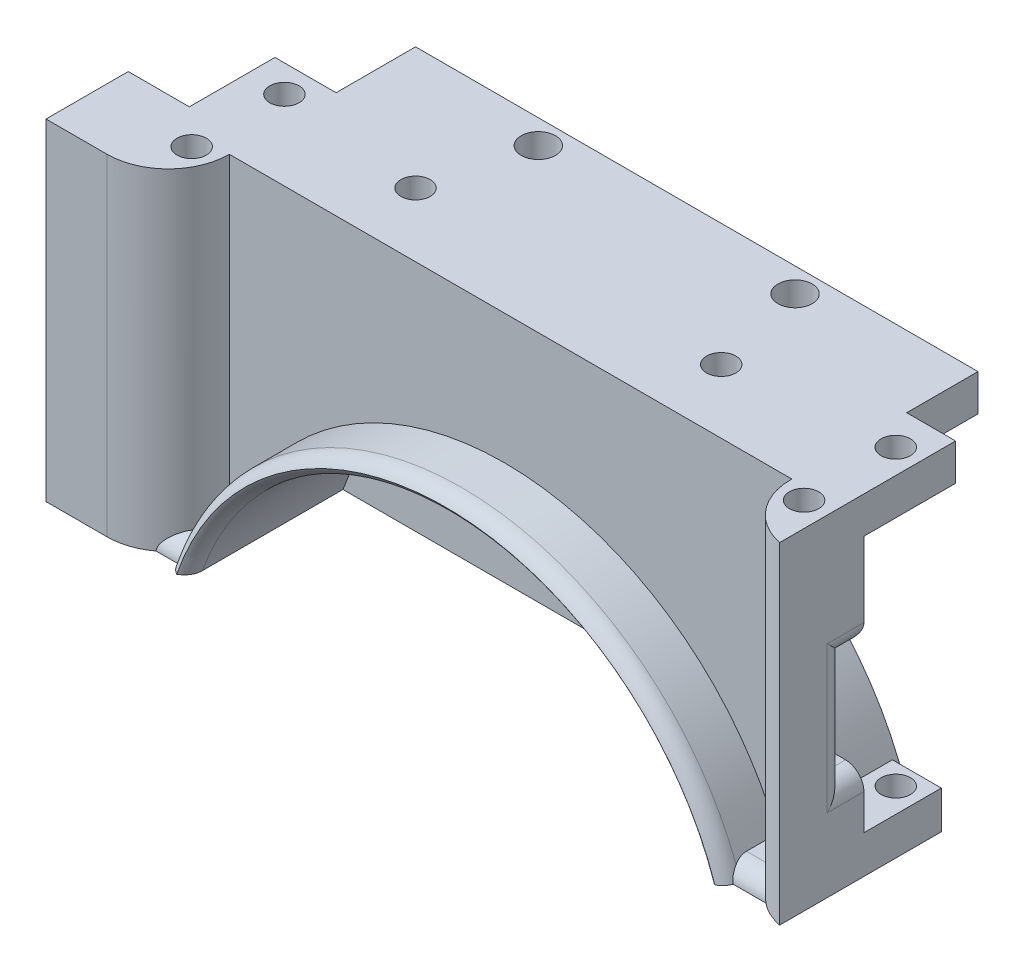
SolidWorks part; units mm, degrees
ref_plane "Front Plane" through (0, 0, 0) normal (0, 0, 1) x (1, 0, 0)
ref_plane "Top Plane" through (0, 0, 0) normal (0, 1, 0) x (1, 0, 0)
ref_plane "Right Plane" through (0, 0, 0) normal (1, 0, 0) x (0, 0, -1)
sketch "Sketch1" plane through (0, 0, 0) normal (0, 1, 0) x (1, 0, 0)
  line L0 (10, 3.275) -> (110, 3.275)
  line L1 (-10, -6.725) -> (10, -6.725)
  line L2 (-10, -6.725) -> (-10, 6.725)
  line L3 (-10, 6.725) -> (0, 6.725)
  line L4 (10, -6.725) -> (10, 3.275)
  line L5 (10, 6.725) -> (102, 6.725)
  line L6 (0, 6.725) -> (0, 20.725)
  line L7 (110, 3.275) -> (110, 6.725)
  line L8 (0, 20.725) -> (10, 20.725)
  line L9 (10, 20.725) -> (10, 6.725)
  line L10 (110, 6.725) -> (110, 19.725)
  line L11 (110, 19.725) -> (102, 19.725)
  line L12 (102, 19.725) -> (102, 6.725)
  point P0 (0, 0)
  dimension "D1" = 20
  dimension "D2" = 13.45
  dimension "D3" = 10
  dimension "D4" = 100
  dimension "D5" = 13
  dimension "D6" = 8
  dimension "D7" = 14
extrude "Boss-Extrude2" add sketch "Sketch1" along normal blind 54.2
fillet "Fillet2" radius 10 1 edges at (10, 27.1, 6.725)
sketch "Sketch2" plane through (0, 0, -3.275) normal (0, 0, 1) x (1, 0, 0)
  line L0 (10, 54.2) -> (110, 54.2) construction
  line L1 (110, 0) -> (102, 0)
  line L2 (110, 0) -> (110, 54.2)
  line L3 (110, 54.2) -> (102, 54.2)
  line L4 (102, 0) -> (102, 54.2)
  dimension "D1" = 8
extrude "Boss-Extrude3" add sketch "Sketch2" along normal blind 10
fillet "Fillet3" radius 10 1 edges at (102, 27.1, 6.725)
sketch "Sketch3" plane through (0, 0, -3.275) normal (0, 0, 1) x (1, 0, 0)
  line L1 (10, 0) -> (102, 0) construction
  line L2 (7, -15) -> (103, -15)
  line L3 (10, 54.2) -> (10, 0) construction
  arc A0 (103, -15) -> (7, -15) centre (55, -15) ccw
  dimension "D1" = 15
  dimension "D2" = 45
  dimension "D3" = 48
extrude "Boss-Extrude4" add sketch "Sketch3" along normal blind 10 and the other way blind 20
sketch "Sketch4" plane through (0, 0, 6.725) normal (0, 0, 1) x (1, 0, 0)
  line L0 (7, -15) -> (103, -15) construction
  circle A0 centre (55, -15) radius 45
  dimension "D1" = 90
extrude "Cut-Extrude1" cut sketch "Sketch4" against normal through all
sketch "Sketch5" plane through (0, 0, 6.725) normal (0, 0, 1) x (1, 0, 0)
  line L0 (9.4039, 0) -> (100.5961, 0)
  line L1 (7, -15) -> (10, -15) construction
  line L2 (10, -15) -> (105.9097, -15)
  line L3 (105.9097, -15) -> (100.5961, 0)
  arc A0 (100, -15) -> (10, -15) centre (55, -15) ccw construction
  spline S0 degree 2 poles (9.4039, 0) (-0.8331, -16.4811) (10, -15) knots 0 0 0 1 1 1
  arc M5 (10, -15) -> (100, -15) centre (55, -15) cw
extrude "Cut-Extrude2" cut sketch "Sketch5" against normal through all contours L2 L0 M5
fillet "Fillet4" radius 3 2 edges at (55, 33, 6.725) (55, 30, 6.725)
sketch "Sketch6" plane through (0, 0, -3.275) normal (0, 0, 1) x (1, 0, 0)
  line L1 (102, 0) -> (97.9701, 0)
  line L2 (102, 0) -> (102, 2.7714)
  line L3 (102, 2.7714) -> (97.9701, 2.7714)
  line L4 (97.9701, 0) -> (97.9701, 2.7714)
  arc A0 (99.0142, 0) -> (10.9858, 0) centre (55, -15) ccw construction
  dimension "D1" = 2.7714
extrude "Boss-Extrude5" add sketch "Sketch6" along normal blind 8
sketch "Sketch7" plane through (102, 0, 0) normal (1, 0, 0) x (0, 0, -1)
  line L1 (3.073, 0) -> (-4.725, 0)
  line L2 (3.073, 0) -> (3.073, 2.7714)
  line L3 (3.073, 2.7714) -> (-4.725, 2.7714)
  line L4 (-4.725, 0) -> (-4.725, 2.7714)
extrude "Boss-Extrude6" add sketch "Sketch7" along normal up to surface (3.7397 mm away)
fillet "Fillet5" radius 3 1 edges at (102.572, 2.7714, 4.725)
sketch "Sketch8" plane through (0, 0, -3.275) normal (0, 0, 1) x (1, 0, 0)
  line L1 (10.5642, 0) -> (7.2004, 0)
  line L2 (10.5642, 0) -> (10.5642, 2.77)
  line L3 (10.5642, 2.77) -> (7.2004, 2.77)
  line L4 (7.2004, 0) -> (7.2004, 2.77)
  line L5 (9.4039, 0) -> (10.9858, 0) construction
extrude "Boss-Extrude7" add sketch "Sketch8" along normal blind 8
sketch "Sketch9" plane through (7.2004, 0, 0) normal (-1, 0, 0) x (0, 0, 1)
  line L1 (3.6643, 0) -> (4.725, 0)
  line L2 (3.6643, 0) -> (3.6643, 2.77)
  line L3 (3.6643, 2.77) -> (4.725, 2.77)
  line L4 (4.725, 0) -> (4.725, 2.77)
extrude "Boss-Extrude8" add sketch "Sketch9" along normal up to surface up to face at (6.2429, 18.99, 2.8841)
fillet "Fillet12" radius 3 1 edges at (8.2821, 2.77, 4.725)
sketch "Sketch10" plane through (0, 54.2, 0) normal (0, 1, 0) x (1, 0, 0)
  line L0 (110, -6.725) -> (110, 19.725) construction
  line L1 (102, 19.725) -> (110, 19.725)
  line L2 (102, 19.725) -> (102, 13.0613)
  line L3 (102, 13.0613) -> (110, 13.0613)
  line L4 (110, 19.725) -> (110, 13.0613)
extrude "Cut-Extrude3" cut sketch "Sketch10" against normal blind 48
sketch "Sketch15" plane through (0, 0, -23.275) normal (0, 0, -1) x (-1, 0, 0)
  line L0 (-97.4264, 0) -> (-12.5736, 0)
  arc A0 (-12.5736, 0) -> (-97.4264, 0) centre (-55, -14.6489) ccw
extrude "Boss-Extrude10" add sketch "Sketch15" against normal blind 4 contours A0 L0
sketch "Sketch16" plane through (0, 0, -6.725) normal (0, 0, -1) x (-1, 0, 0)
  line L0 (-10, 54.2) -> (-10, 1.7033) construction
  line L1 (-102, 54.2) -> (-10, 54.2)
  line L2 (-102, 54.2) -> (-102, 48.2)
  line L3 (-102, 48.2) -> (-10, 48.2)
  line L4 (-10, 54.2) -> (-10, 48.2)
  dimension "D1" = 6
extrude "Boss-Extrude11" add sketch "Sketch16" along normal blind 27
sketch "Sketch17" plane through (0, 54.2, 0) normal (0, 1, 0) x (1, 0, 0)
  circle A0 centre (106, 16.275) radius 2.4
  circle A1 centre (106, 1.275) radius 2.4
  circle A2 centre (76.027, 29.775) radius 2.8
  circle A3 centre (34.027, 29.775) radius 2.8
  circle A4 centre (6, 16.275) radius 2.4
  circle A5 centre (5.83, 1.275) radius 2.4
  dimension "D1" = 4.8
  dimension "D2" = 4.8
  dimension "D3" = 4.8
  dimension "D4" = 4.8
  dimension "D5" = 5.6
  dimension "D6" = 5.6
sketch "Sketch18" plane through (0, 0, -13.0613) normal (0, 0, -1) x (-1, 0, 0)
  line L1 (-110, 54.2) -> (-102, 54.2)
  line L2 (-110, 54.2) -> (-110, 48.2)
  line L3 (-110, 48.2) -> (-102, 48.2)
  line L4 (-102, 54.2) -> (-102, 48.2)
extrude "Boss-Extrude12" add sketch "Sketch18" along normal blind 9
sketch "Sketch20" plane through (0, 0, -6.725) normal (0, 0, -1) x (-1, 0, 0)
  line L0 (-102, 43.3091) -> (-10, 43.3091) construction
  line L1 (-102, 6.2) -> (-102, 48.2) construction
  line L2 (-10, 48.2) -> (-10, 1.7033) construction
ref_plane "Plane1" through (55, 0, 0) normal (1, 0, 0) x (0, 0, -1)
sketch "Sketch26" plane through (55, 0, 0) normal (1, 0, 0) x (0, 0, -1)
  line L1 (6.8887, 51.2053) -> (6.725, 33)
  line L4 (33.725, 48.2) -> (22.0613, 48.2) construction
  line L5 (23.2583, 48.2) -> (6.8887, 51.2053)
  line L6 (6.725, 33) -> (23.2583, 48.2)
extrude "Boss-Extrude15" add sketch "Sketch26" along normal blind 47 and the other way blind 45 separate body
extrude "Cut-Extrude6" cut sketch "Sketch17" against normal through all
sketch "Sketch28" plane through (0, 54.2, 0) normal (0, 1, 0) x (1, 0, 0)
  line L0 (0, 13.725) -> (110, 13.725) construction
  line L1 (0, 20.725) -> (0, 6.725) construction
  line L2 (110, -6.725) -> (110, 22.0613) construction
  circle A0 centre (30, 13.725) radius 2.4
  circle A1 centre (80, 13.725) radius 2.4
  dimension "D1" = 4.8
  dimension "D2" = 4.8
  dimension "D3" = 50
  dimension "D4" = 30
extrude "Cut-Extrude7" cut sketch "Sketch28" against normal blind 9
sketch "Sketch29" plane through (0, 0, -6.725) normal (0, 0, -1) x (-1, 0, 0)
  line L0 (-9.4039, 0) -> (-100.5961, 0) construction
  line L1 (-103.2355, 2.7375) -> (-98.8805, 2.7375)
  line L2 (-103.2355, 2.7375) -> (-103.2355, 0)
  line L3 (-103.2355, 0) -> (-98.8805, 0)
  line L4 (-98.8805, 2.7375) -> (-98.8805, 0)
  line L5 (-110, 0) -> (-102, 0) construction
extrude "Boss-Extrude16" add sketch "Sketch29" along normal blind 12
sketch "Sketch30" plane through (0, 0, -13.0613) normal (0, 0, -1) x (-1, 0, 0)
  line L1 (-110, 48.2) -> (-102, 48.2)
  line L2 (-110, 48.2) -> (-110, 6.2)
  line L3 (-110, 6.2) -> (-102, 6.2)
  line L4 (-102, 48.2) -> (-102, 6.2)
extrude "Cut-Extrude9" cut sketch "Sketch30" against normal blind 6
sketch "Sketch31" plane through (0, 0, -7.0613) normal (0, 0, -1) x (-1, 0, 0)
  line L3 (-110.1013, 24) -> (-102, 24)
  line L5 (-102, 48.2) -> (-102, 2.7375) construction
  line L6 (-110, 0) -> (-102, 0) construction
  line L7 (-102, 6.2) -> (-102, 48.2) construction
  line L8 (-110.1013, 15.0261) -> (-102, 15.0261)
  line L9 (-110.1013, 15.0261) -> (-110.1013, 32.9739)
  line L10 (-110.1013, 32.9739) -> (-102, 32.9739)
  line L11 (-102, 15.0261) -> (-102, 32.9739)
  line L12 (-110.1013, 15.0261) -> (-102, 32.9739) construction
  line L13 (-110.1013, 32.9739) -> (-102, 15.0261) construction
  point P0 (-106.0506, 24)
  line M2 (-110, 48.2) -> (-110, 6.2)
  line M4 (-102, 6.2) -> (-102, 48.2)
  dimension "D1" = 24
extrude "Cut-Extrude16" cut sketch "Sketch31" against normal blind 3 contours L10 L3 M2 M4 | L8 L3 M2 M4
fillet "Fillet14" radius 3 5 edges at (102, 24, -4.0613) (110, 24, -4.0613) (110, 15.0261, -5.5613) (106, 32.9739, -7.0613) (110, 32.9739, -5.5613)
ref_plane "Plane2" through (-10, 0, 0) normal (1, 0, 0) x (0, 0, -1)
mirror "Mirror12" [suppressed] about plane through (-10, 0, 0) normal (1, 0, 0)
